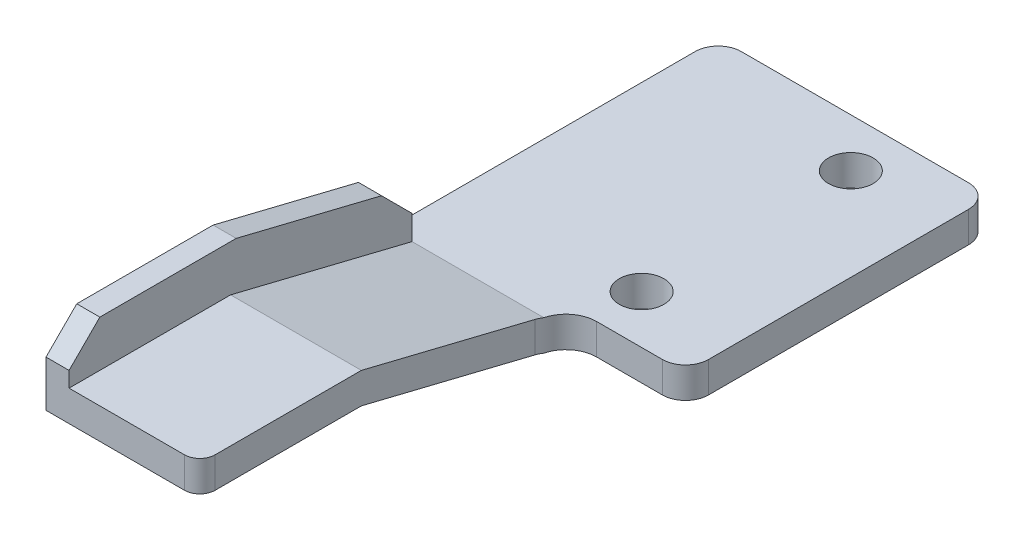
SolidWorks part; units mm, degrees
ref_plane "Front Plane" through (0, 0, 0) normal (0, 0, 1) x (1, 0, 0)
ref_plane "Top Plane" through (0, 0, 0) normal (0, 1, 0) x (1, 0, 0)
ref_plane "Right Plane" through (0, 0, 0) normal (1, 0, 0) x (0, 0, -1)
sketch "Sketch1" plane through (0, 0, 0) normal (0, 1, 0) x (1, 0, 0)
  line L0 (2.885, 6.8) -> (2.885, -6.8) construction
  line L1 (8.885, 9.95) -> (-8.885, 9.95)
  line L2 (8.885, 9.95) -> (8.885, -9.95)
  line L3 (8.885, -9.95) -> (-8.885, -9.95)
  line L4 (-8.885, 9.95) -> (-8.885, -9.95)
  line L5 (8.885, 9.95) -> (-8.885, -9.95) construction
  line L6 (8.885, -9.95) -> (-8.885, 9.95) construction
  circle A0 centre (2.885, 6.8) radius 1.45
  circle A1 centre (2.885, -6.8) radius 1.45
  point P0 (0, 0)
  point P8 (2.885, 0)
  dimension "D3" = 6
  dimension "D5" = 2.9
  dimension "D1" = 19.9
  dimension "D2" = 13.6
  dimension "D4" = 11.77
extrude "Boss-Extrude1" add sketch "Sketch1" along normal blind 2
sketch "Sketch2" plane through (-8.885, 0, 0) normal (-1, 0, 0) x (0, 0, 1)
  line L0 (9.95, 2) -> (11.45, 2)
  line L1 (11.45, 2) -> (23.25, 4.9)
  line L2 (23.25, 4.9) -> (33.75, 4.9)
  line L3 (9.95, 0) -> (11.45, 0)
  line L4 (11.45, 0) -> (23.25, 2.9)
  line L5 (23.25, 2.9) -> (33.75, 2.9)
  line L6 (33.75, 2.9) -> (33.75, 4.9)
  line L7 (11.45, 2) -> (11.45, 0) construction
  line L8 (23.25, 2.9) -> (23.25, 4.9) construction
  line L9 (-9.95, 0) -> (9.95, 0) construction
  line L10 (9.95, 2) -> (9.95, 0)
  dimension "D1" = 2.9
  dimension "D2" = 2
  dimension "D3" = 13.3
  dimension "D4" = 10.5
  dimension "D5" = 1.5
extrude "Boss-Extrude2" add sketch "Sketch2" against normal blind 10
sketch "Sketch4" plane through (-8.885, 0, 0) normal (-1, 0, 0) x (0, 0, 1)
  line L0 (33.75, 4.9) -> (23.25, 4.9) construction
  line L1 (23.25, 4.9) -> (11.45, 2) construction
  line L2 (33.75, 4.9) -> (23.25, 4.9)
  line L3 (23.25, 4.9) -> (11.45, 2)
  line L6 (33.75, 7.9) -> (22.8868, 7.9)
  line L7 (22.8868, 7.9) -> (11.45, 5.0893)
  line L9 (33.75, 4.9) -> (33.75, 7.9)
  line L11 (-8.8807, 10.0858) -> (11.45, 5.0893) construction
  line L12 (-9.5967, 7.1725) -> (11.45, 2) construction
  line L13 (11.45, 5.0893) -> (11.45, 2)
  dimension "D1" = 3
extrude "Boss-Extrude4" add sketch "Sketch4" against normal blind 1.5
chamfer "Chamfer1" distance 2 angle 45 1 edges at (-8.135, 7.9, 33.75)
chamfer "Chamfer2" distance 1.5 angle 45 1 edges at (-8.135, 5.0893, 11.45) first distance on face at (-8.135, 3.5446, 11.45)
fillet "Fillet1" radius 1.5 3 edges at (8.885, 1, 9.95) (8.885, 1, -9.95) (-8.885, 1, -9.95)
fillet "Fillet2" radius 1 1 edges at (1.115, 3.9, 33.75)
fillet "Fillet3" radius 2 1 edges at (1.115, 1, 9.95)
